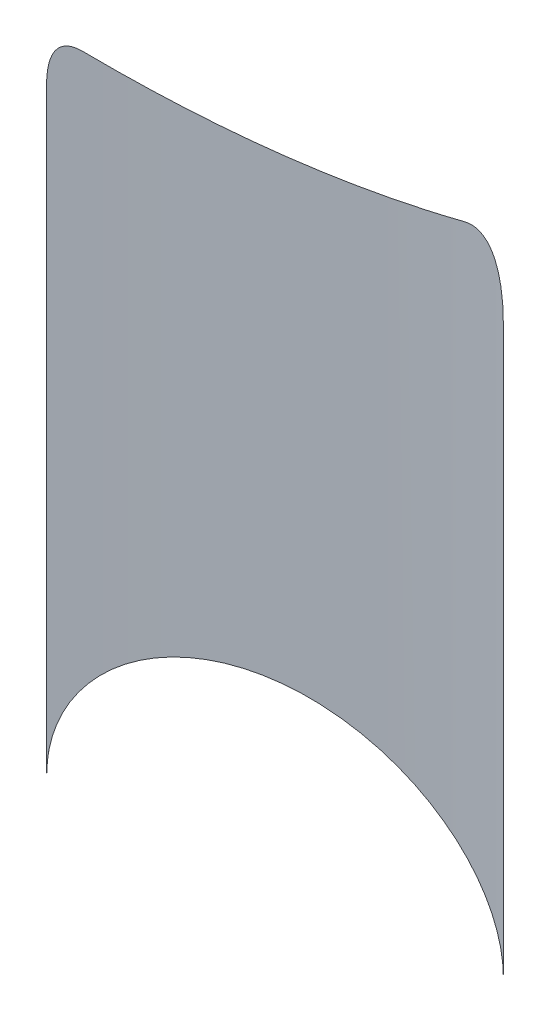
SolidWorks part; units mm, degrees
ref_plane "Front Plane" through (0, 0, 0) normal (0, 0, 1) x (1, 0, 0)
ref_plane "Top Plane" through (0, 0, 0) normal (0, 1, 0) x (1, 0, 0)
ref_plane "Right Plane" through (0, 0, 0) normal (1, 0, 0) x (0, 0, -1)
sketch "Sketch1" plane through (0, 0, 0) normal (0, 1, 0) x (1, 0, 0)
  line L0 (0, 0) -> (-8.9803, -8.9803)
  line L1 (-8.9803, -8.9803) -> (8.9803, -8.9803)
  line L2 (8.9803, -8.9803) -> (0, 0)
  dimension "D1" = 12.7
extrude "Boss-Extrude1" add sketch "Sketch1" along normal blind 25.4
sketch "Sketch2" plane through (0, 0, 0) normal (-0.7071, 0, -0.7071) x (-0.7071, 0, 0.7071)
  line L0 (0, 0) -> (12.7, 0) construction
  line L1 (0, 25.4) -> (0, 0) construction
  circle A0 centre (6.35, 0) radius 6.35
extrude "Cut-Extrude1" cut sketch "Sketch2" against normal up to next
ref_point "Point1"
ref_point "Point2"
ref_point "Point3"
ref_point "Point4"
ref_point "Point5"
ref_axis "Axis1" through (4.4901, 0, 13.4704) along (-0.7071, 0, -0.7071)
sketch "Sketch4" plane through (0, 25.4, 0) normal (0, 1, 0) x (1, 0, 0)
  line L0 (4.4901, -13.4704) -> (-8.9803, 0) construction
  circle A0 centre (9.8382, -90.6605) radius 83.82
  dimension "D2" = 167.64
  dimension "D1" = 50.8
extrude "Cut-Extrude3" cut sketch "Sketch4" against normal through all contours A0
ref_plane "Plane2" through (-0.1779, 0.4984, -1.3527) normal (0.1225, -0.3431, 0.9313) x (0.9925, 0.0424, -0.115)
sketch "Sketch5" plane through (-0.1779, 0.4984, -1.3527) normal (0.1225, -0.3431, 0.9313) x (0.9925, 0.0424, -0.115)
  line L1 (7.1239, 3.9723) -> (-8.8691, 3.9723)
  line L2 (7.1239, 3.9723) -> (7.1239, 26.2165)
  line L3 (7.1239, 26.2165) -> (-8.8691, 26.9384)
  line L4 (-8.8691, 3.9723) -> (-8.8691, 26.9384)
  point P4 (0.1793, 3.9723)
extrude "Cut-Extrude4" cut sketch "Sketch5" against normal up to next
fillet "Fillet1" radius 2.54 2 edges at (3.4461, 14.8167, 3.4461) (-4.4901, 14.8167, 4.4901)
